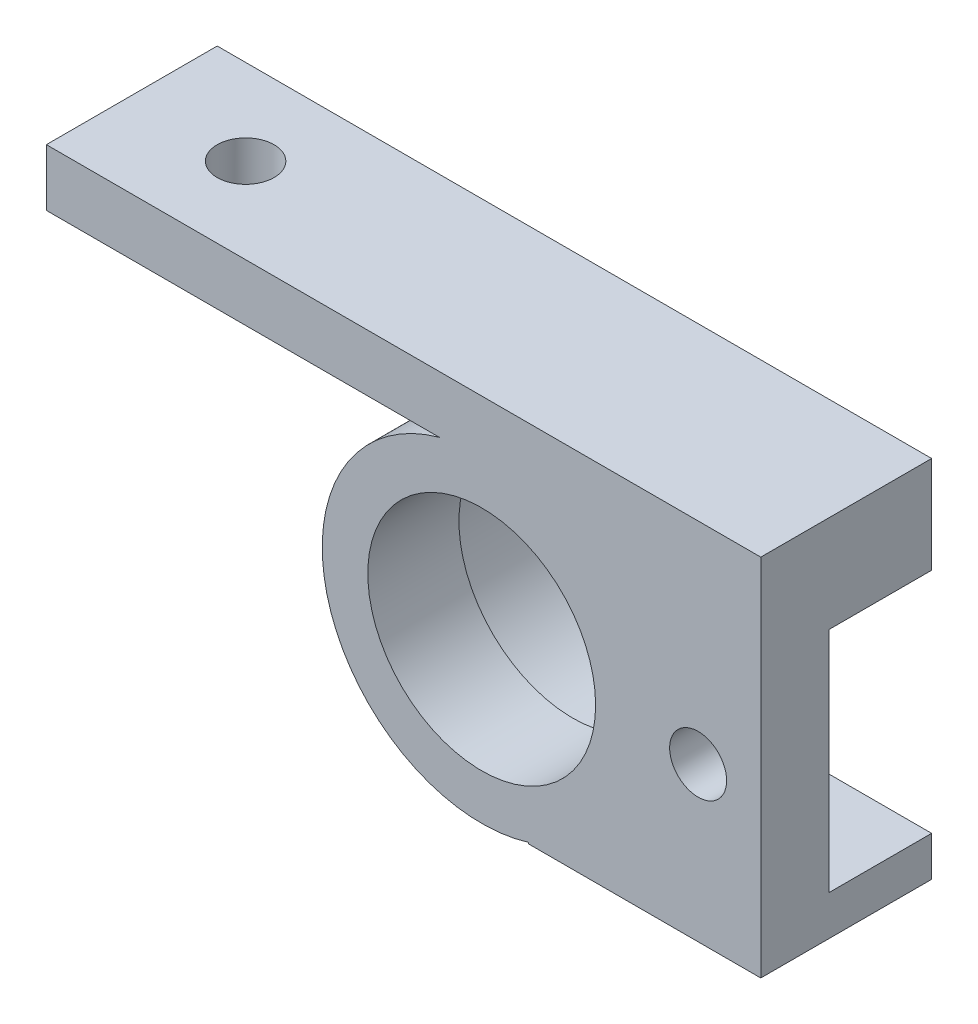
SolidWorks part; units mm, degrees
ref_plane "前视基准面" through (0, 0, 0) normal (0, 0, 1) x (1, 0, 0)
ref_plane "上视基准面" through (0, 0, 0) normal (0, 1, 0) x (1, 0, 0)
ref_plane "右视基准面" through (0, 0, 0) normal (1, 0, 0) x (0, 0, -1)
sketch "草图1" plane through (0, 0, 0) normal (0, 0, 1) x (1, 0, 0)
  line L1 (20, -10) -> (-20, -10)
  line L2 (20, -10) -> (20, 10)
  line L3 (20, 10) -> (-20, 10)
  line L4 (-20, -10) -> (-20, 10)
  line L5 (20, -10) -> (-20, 10) construction
  line L6 (20, 10) -> (-20, -10) construction
  point P0 (0, 0)
  dimension "D1" = 40
  dimension "D2" = 20
extrude "凸台-拉伸1" add sketch "草图1" along normal blind 6
sketch "草图2" plane through (0, 0, 6) normal (0, 0, 1) x (1, 0, 0)
  line L0 (20, -10) -> (20, 10) construction
  circle A0 centre (10, 0) radius 2.5
  circle A1 centre (-1, 0) radius 2.5
  circle A2 centre (-12, 0) radius 2.5
  dimension "D1" = 10
  dimension "D2" = 5
  dimension "D3" = 3
extrude "切除-拉伸1" cut sketch "草图2" against normal through all
sketch "草图3" plane through (0, 0, 6) normal (0, 0, 1) x (1, 0, 0)
  line L0 (20, 13.5) -> (20, 10)
  line L1 (20, -13.5) -> (-26.894, -13.5)
  line L3 (20, 13.5) -> (-26.894, 13.5)
  line L4 (-20, 10) -> (-20, -10)
  line L5 (-20, -10) -> (20, -10)
  line L6 (20, -10) -> (20, 10)
  line L7 (20, 10) -> (-20, 10)
  line L8 (-20, 10) -> (-20, -10)
  line L9 (-20, -10) -> (20, -10)
  line L10 (20, -10) -> (20, 10)
  line L11 (20, 10) -> (-20, 10)
  line L12 (-26.894, -13.5) -> (-26.894, 13.5)
  line L13 (20, -10.0394) -> (-26.894, 13.5) construction
  line L14 (20, 10.0394) -> (-26.894, -13.5) construction
  line L15 (20, -10) -> (20, -13.5)
  circle A0 centre (-31, 0) radius 11
  circle A1 centre (-31, 0) radius 14
  point P2 (0, 0)
  line M10 (-20, 10) -> (-20, -10)
  line M11 (-20, -10) -> (20, -10)
  line M13 (20, 10) -> (-20, 10)
  dimension "D3" = 22
  dimension "D4" = 28
  dimension "D2" = 3.5
  dimension "D1" = 0
extrude "凸台-拉伸2" add sketch "草图3" against normal blind 15 contours L3 A1 L1 L12 A0 | A1 L1 L15 M11 M10 | L1 A1 L8 A0 L12 | L8 A1 L3 L12 A0 | L8 A1 | A1 L0 L3 M10 M13 region at (-1.9449, 11.7771, 6) region at (-1.9449, -11.7771, 6) region at (-23.0173, 9.0328, 6) region at (-27.2274, 11.7946, 6) region at (-18.7882, 0, 6) region at (-23.0173, -9.0328, 6)
sketch "草图5" plane through (0, 0, 6) normal (0, 0, 1) x (1, 0, 0)
  circle A0 centre (-31, 0) radius 10
  circle A1 centre (-31, 0) radius 11 construction
  circle A2 centre (-31, 0) radius 11
  dimension "D1" = 20
extrude "凸台-拉伸3" add sketch "草图5" against normal blind 8
sketch "草图6" plane through (0, 0, 6) normal (0, 0, 1) x (1, 0, 0)
  circle A0 centre (-31, 0) radius 8.5
  circle A1 centre (-31, 0) radius 10 construction
  circle A2 centre (-31, 0) radius 10
  dimension "D1" = 17
sketch "草图7" plane through (0, 13.5, 0) normal (0, 1, 0) x (1, 0, 0)
  circle A0 centre (-17.1666, 1.953) radius 2.6594
sketch "草图8" plane through (20, 0, 0) normal (1, 0, 0) x (0, 0, -1)
  line L1 (-6, 13.5) -> (9, 13.5)
  line L2 (-6, 13.5) -> (-6, 18.5)
  line L3 (-6, 18.5) -> (9, 18.5)
  line L4 (9, 13.5) -> (9, 18.5)
  dimension "D1" = 5
extrude "凸台-拉伸4" add sketch "草图8" against normal blind 500
sketch "草图9" plane through (0, 0, -9) normal (0, 0, -1) x (-1, 0, 0)
  line L1 (24.4567, 15.8334) -> (28.494, 15.8334)
  line L2 (24.4567, 15.8334) -> (24.4567, 12.469)
  line L3 (24.4567, 12.469) -> (28.494, 12.469)
  line L4 (28.494, 15.8334) -> (28.494, 12.469)
extrude "凸台-拉伸5" add sketch "草图9" against normal through all
sketch "草图10" plane through (0, 0, 6) normal (0, 0, 1) x (1, 0, 0)
  line L0 (-12, 0) -> (-1, 0) construction
  line L1 (-6.5, 0) -> (-6.5, 18.5) construction
  line L2 (-480, 18.5) -> (20, 18.5) construction
  line L4 (-6.5, 18.5) -> (20, 18.5)
  line L5 (-6.5, 18.5) -> (-6.5, -13.5)
  line L6 (-6.5, -13.5) -> (20, -13.5)
  line L7 (20, 18.5) -> (20, -13.5)
extrude "切除-拉伸2" cut sketch "草图10" against normal through all
sketch "草图11" plane through (0, 18.5, 0) normal (0, 1, 0) x (1, 0, 0)
  line L0 (-69.2198, 9) -> (-69.2198, -6.0139)
  line L1 (-480, 9) -> (-6.5, 9) construction
  line L2 (-69.2198, 251.4142) -> (-69.2198, -118.5858) construction
sketch "草图12" plane through (0, 18.5, 0) normal (0, 1, 0) x (1, 0, 0)
  line L1 (-69.2198, -6.0139) -> (-501.7351, -6.0139)
  line L2 (-69.2198, -6.0139) -> (-69.2198, 21.5219)
  line L3 (-69.2198, 21.5219) -> (-501.7351, 21.5219)
  line L4 (-501.7351, -6.0139) -> (-501.7351, 21.5219)
extrude "切除-拉伸3" cut sketch "草图12" against normal through all
sketch "草图13" plane through (0, 18.5, 0) normal (0, 1, 0) x (1, 0, 0)
  line L0 (-69.2198, 1.493) -> (-59.2198, 1.493) construction
  line L1 (-69.2198, 9) -> (-69.2198, -6.0139) construction
  circle A0 centre (-59.2198, 1.493) radius 2.5
  dimension "D1" = 5
  dimension "D2" = 10
extrude "切除-拉伸4" cut sketch "草图13" against normal through all
